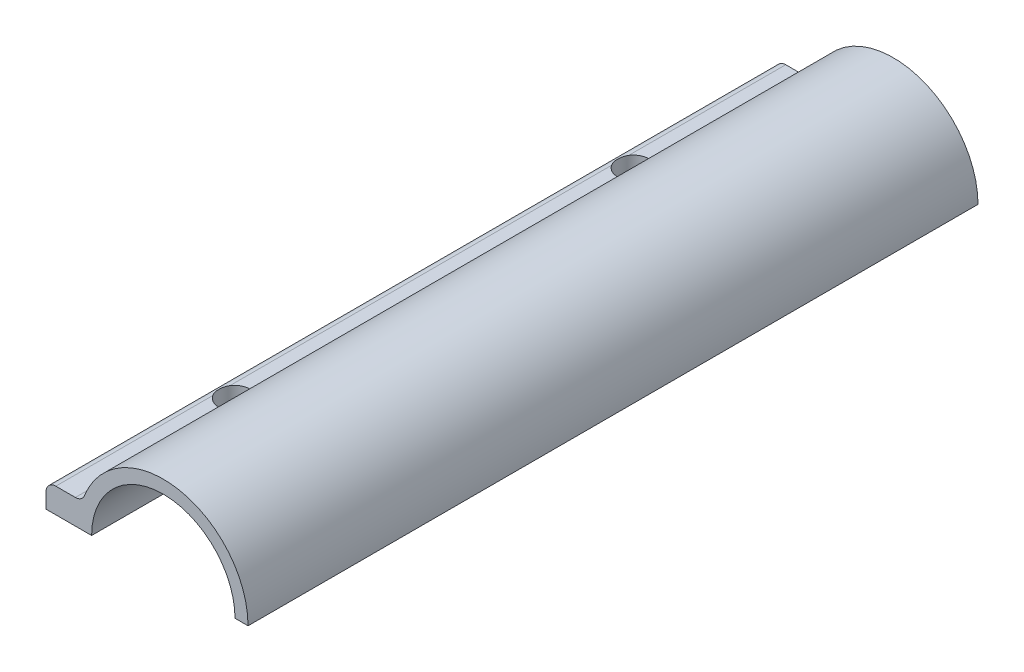
SolidWorks part; units mm, degrees
material "ABS"
ref_plane "X-Y Datum" through (0, 0, 0) normal (0, 0, 1) x (1, 0, 0)
ref_plane "X-Z Datum" through (0, 0, 0) normal (0, 1, 0) x (1, 0, 0)
ref_plane "Y-Z Datum" through (0, 0, 0) normal (1, 0, 0) x (0, 0, -1)
sketch "Sketch1" plane through (0, 0, 0) normal (0, 0, 1) x (1, 0, 0)
  line L0 (-13, 0) -> (-18, 0)
  line L1 (-18, 0) -> (-18, -13)
  line L2 (-18, -13) -> (0, -13)
  line L3 (-13, 0) -> (13, 0)
  line L4 (0, 13) -> (-18, 13)
  line L5 (-18, 13) -> (-18, 0)
  line L6 (-18, 3.81) -> (-12.4292, 3.81)
  circle A0 centre (0, 0) radius 13
  circle A1 centre (0, 0) radius 11
  dimension "D3" = 2
  dimension "D2" = 22
  dimension "D1" = 5
  dimension "D4" = 3.81
extrude "Boss-Extrude1" add sketch "Sketch1" along normal blind 112 contours A1 L3 A0 | A0 L6 L5 L0 region at (-12.569, 1.8832, 0) region at (-15.4029, 1.9398, 0)
sketch "Sketch5" plane through (0, 3.81, 0) normal (0, 1, 0) x (1, 0, 0)
  point P0 (-14.5, -86.6)
  point P1 (-14.5, -25.4)
hole_wizard "M4 Clearance Hole2" positions "Sketch5" profile "Sketch6" hole size "M4" standard "ANSI Metric" end condition through all
sketch "Sketch6" plane through (-14.5, 3.81, 86.6) normal (1, 0, 0) x (0, 0, 1)
  line L0 (0, 0) -> (0, 3.81)
  line L1 (0, 3.81) -> (2.4, 3.81)
  line L2 (2.4, 3.81) -> (2.4, 0)
  line L5 (2.4, 0) -> (0, 0)
  line L11 (0, -6.35) -> (0, 107.95) construction
  dimension "Thru Hole Dia." = 4.8
  dimension "Thru Hole Depth" = 3.81
sketch "Sketch7" plane through (0, 3.81, 0) normal (0, 1, 0) x (1, 0, 0)
  circle A0 centre (-14.5, -25.4) radius 4
  circle A1 centre (-14.5, -86.6) radius 4
  dimension "D1" = 8
extrude "Cut-Extrude1" cut sketch "Sketch7" along normal through all
fillet "Fillet1" radius 1.5 4 edges at (-12.4292, 3.81, 101.0111) (-12.4292, 3.81, 56) (-18, 3.81, 56) (-12.4292, 3.81, 10.9889)
